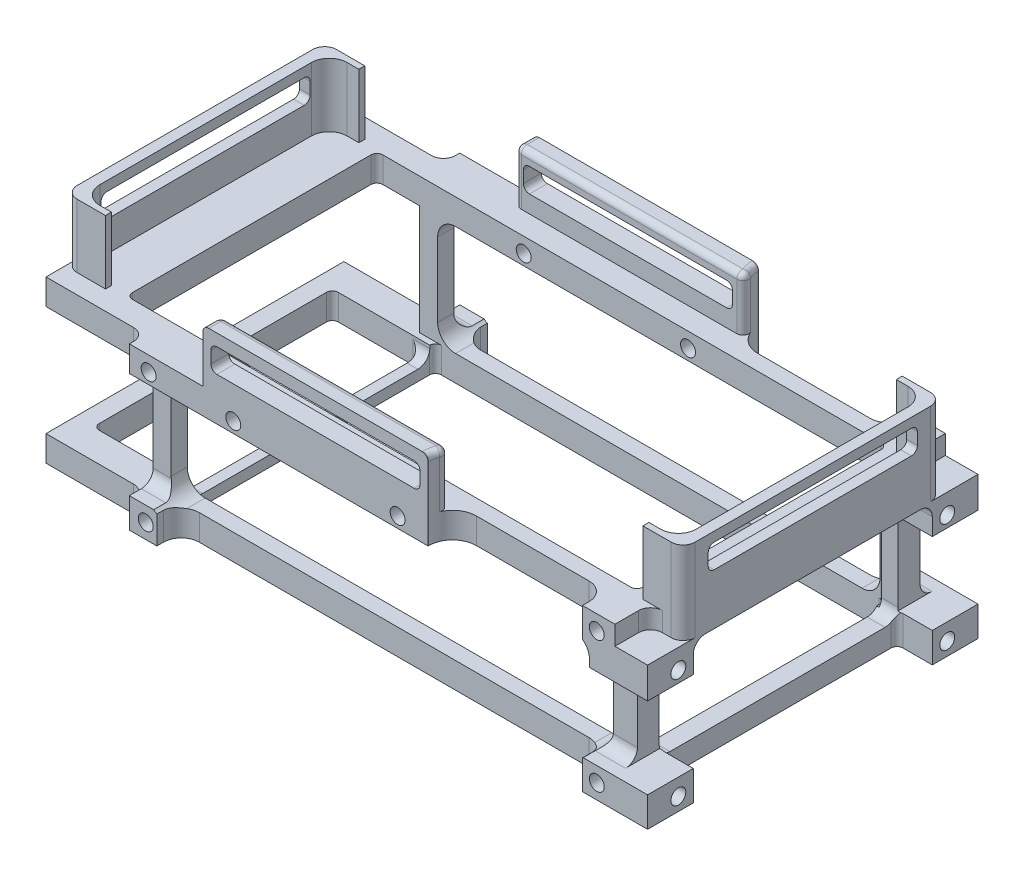
SolidWorks part; units mm, degrees
ref_plane "Front" through (0, 0, 0) normal (0, 0, 1) x (1, 0, 0)
ref_plane "Top" through (0, 0, 0) normal (0, 1, 0) x (1, 0, 0)
ref_plane "Right" through (0, 0, 0) normal (1, 0, 0) x (0, 0, -1)
sketch "草图1" plane through (0, 0, 0) normal (0, 1, 0) x (1, 0, 0)
  line L0 (-68.9333, 0) -> (79.9935, 0) construction
  line L1 (-51.7, 24.925) -> (-37.03, 24.925)
  line L2 (-35.03, 27.65) -> (-30.42, 27.65)
  line L3 (-51.7, 24.925) -> (-51.7, -24.925)
  line L4 (-35.03, -27.65) -> (-30.42, -27.65)
  line L5 (51.7, 27.65) -> (51.7, -27.65)
  line L8 (-35.03, 26.925) -> (-35.03, 27.65)
  line L9 (-30.42, 27.65) -> (-30.42, 26.55)
  line L10 (-27.42, 23.55) -> (37.8, 23.55)
  line L11 (40.8, 26.55) -> (40.8, 27.65)
  line L12 (40.8, 27.65) -> (51.7, 27.65)
  line L13 (-51.7, -24.925) -> (-37.03, -24.925)
  line L14 (-35.03, -26.925) -> (-35.03, -27.65)
  line L16 (-30.42, -27.65) -> (-30.42, -26.55)
  line L17 (-27.42, -23.55) -> (37.8, -23.55)
  line L18 (40.8, -26.55) -> (40.8, -27.65)
  line L19 (40.8, -27.65) -> (51.7, -27.65)
  arc A0 (37.8, -23.55) -> (40.8, -26.55) centre (37.8, -26.55) cw
  arc A1 (-30.42, -26.55) -> (-27.42, -23.55) centre (-27.42, -26.55) cw
  arc A2 (-30.42, 26.55) -> (-27.42, 23.55) centre (-27.42, 26.55) ccw
  arc A3 (37.8, 23.55) -> (40.8, 26.55) centre (37.8, 26.55) ccw
  arc A4 (-37.03, -24.925) -> (-35.03, -26.925) centre (-37.03, -26.925) cw
  arc A5 (-37.03, 24.925) -> (-35.03, 26.925) centre (-37.03, 26.925) ccw
  point P5 (0, 0)
  point P27 (-30.42, -23.55)
  point P30 (-30.42, 23.55)
  point P37 (-35.03, 24.925)
  dimension "D9" = 3
  dimension "D10" = 2
  dimension "D1" = 103.4
  dimension "D2" = 55.3
  dimension "D3" = 49.85
  dimension "D4" = 47.1
  dimension "D5" = 10.9
  dimension "D6" = 16.67
  dimension "D7" = 4.61
  dimension "D8" = 51.7
extrude "凸台-拉伸1" add sketch "草图1" along normal blind 27
sketch "草图2" plane through (0, 0, 0) normal (0, 0, 1) x (1, 0, 0)
  line L0 (-60.618, 13.5) -> (64.0258, 13.5) construction
  line L1 (-51.7, 22.7) -> (-35.03, 22.7)
  line L2 (-51.7, 27) -> (-51.7, 0) construction
  line L3 (-35.03, 27) -> (-35.03, 0) construction
  line L4 (-35.03, 22.7) -> (-35.03, 4.3)
  line L5 (-35.03, 4.3) -> (-51.7, 4.3)
  line L6 (-51.7, 4.3) -> (-58.4494, 4.3)
  line L7 (-58.4494, 4.3) -> (-58.4494, 22.7)
  line L8 (-58.4494, 22.7) -> (-51.7, 22.7)
  line L9 (-30.42, 27) -> (-30.42, 0) construction
  line L10 (-32.03, 19.7) -> (-32.03, 7.3)
  line L11 (-29.03, 4.3) -> (39, 4.3)
  line L12 (42, 7.3) -> (42, 19.7)
  line L13 (39, 22.7) -> (-29.03, 22.7)
  line L14 (51.7, 5) -> (46, 5)
  line L15 (51.7, 27) -> (51.7, 0) construction
  line L16 (46, 5) -> (46, 18.6)
  line L17 (46, 18.6) -> (55.971, 18.6)
  line L18 (55.971, 18.6) -> (51.7, 5)
  line L19 (40.8, 0) -> (51.7, 0) construction
  arc A0 (39, 4.3) -> (42, 7.3) centre (39, 7.3) ccw
  arc A1 (42, 19.7) -> (39, 22.7) centre (39, 19.7) ccw
  arc A2 (-29.03, 4.3) -> (-32.03, 7.3) centre (-29.03, 7.3) cw
  arc A3 (-32.03, 19.7) -> (-29.03, 22.7) centre (-29.03, 19.7) cw
  point P14 (-30.42, 13.5)
  dimension "D8" = 3
  dimension "D1" = 18.4
  dimension "D2" = 3
  dimension "D3" = 13.6
  dimension "D4" = 5
  dimension "D5" = 5.7
  dimension "D6" = 4
  dimension "D7" = 18.4
extrude "切除-拉伸1" cut sketch "草图2" against normal through all both and the other way through all
sketch "草图3" plane through (0, 27, 0) normal (0, 1, 0) x (1, 0, 0)
  line L0 (-59.4821, 0) -> (58.6559, 0) construction
  line L1 (-41.2022, 20.95) -> (42.2, 20.95)
  line L2 (-42.2022, 19.95) -> (-42.2022, -19.95)
  line L3 (-41.2022, -20.95) -> (42.2, -20.95)
  line L4 (43.2, 19.95) -> (43.2, -19.95)
  line L5 (51.7, -27.65) -> (51.7, 27.65) construction
  line L6 (37.8, 23.55) -> (-27.42, 23.55) construction
  arc A0 (-41.2022, 20.95) -> (-42.2022, 19.95) centre (-41.2022, 19.95) ccw
  arc A1 (-42.2022, -19.95) -> (-41.2022, -20.95) centre (-41.2022, -19.95) ccw
  arc A2 (42.2, -20.95) -> (43.2, -19.95) centre (42.2, -19.95) ccw
  arc A3 (42.2, 20.95) -> (43.2, 19.95) centre (42.2, 19.95) cw
  dimension "D4" = 1
  dimension "D1" = 8.5
  dimension "D2" = 85.4022
  dimension "D3" = 2.6
extrude "切除-拉伸2" cut sketch "草图3" against normal up to surface (22.7 mm away) up to face at (-41.1153, 4.3, 0)
sketch "草图4" plane through (0, 0, 0) normal (0, -1, 0) x (1, 0, 0)
  line L0 (-62.5801, 0) -> (74.4559, 0) construction
  line L1 (51.7, 27.65) -> (51.7, -27.65) construction
  line L2 (-47.7, 20) -> (-35.2, 20)
  line L3 (-48.7, 19) -> (-48.7, -19)
  line L4 (-47.7, -20) -> (-35.2, -20)
  line L5 (-34.2, 19) -> (-34.2, -19)
  line L6 (41.8, 20.95) -> (-31.4, 20.95)
  line L7 (42.8, 19.95) -> (42.8, -19.95)
  line L8 (41.8, -20.95) -> (-31.4, -20.95)
  line L9 (-32.4, 19.95) -> (-32.4, -19.95)
  line L10 (46.8, 20) -> (63.9751, 20)
  line L11 (45.8, 19) -> (45.8, -19)
  line L12 (46.8, -20) -> (63.9751, -20)
  line L13 (63.9751, 20) -> (63.9751, -20)
  line L15 (39, 20.95) -> (42.2, 20.95) construction
  line L16 (42.2, -20.95) -> (-41.2022, -20.95) construction
  line L17 (-51.7, -24.925) -> (-51.7, 24.925) construction
  arc A0 (45.8, -19) -> (46.8, -20) centre (46.8, -19) ccw
  arc A1 (46.8, 20) -> (45.8, 19) centre (46.8, 19) ccw
  arc A2 (42.8, -19.95) -> (41.8, -20.95) centre (41.8, -19.95) cw
  arc A3 (41.8, 20.95) -> (42.8, 19.95) centre (41.8, 19.95) cw
  arc A4 (-31.4, 20.95) -> (-32.4, 19.95) centre (-31.4, 19.95) ccw
  arc A5 (-31.4, -20.95) -> (-32.4, -19.95) centre (-31.4, -19.95) cw
  arc A6 (-35.2, -20) -> (-34.2, -19) centre (-35.2, -19) ccw
  arc A7 (-35.2, 20) -> (-34.2, 19) centre (-35.2, 19) cw
  arc A8 (-47.7, 20) -> (-48.7, 19) centre (-47.7, 19) ccw
  arc A9 (-48.7, -19) -> (-47.7, -20) centre (-47.7, -19) ccw
  dimension "D6" = 1
  dimension "D7" = 1
  dimension "D1" = 5.9
  dimension "D2" = 40
  dimension "D3" = 3
  dimension "D4" = 3
  dimension "D5" = 1.8
  dimension "D8" = 14.5
extrude "切除-拉伸3" cut sketch "草图4" against normal blind 5
sketch "草图5" plane through (0, 0, 0) normal (1, 0, 0) x (0, 0, -1)
  line L0 (0, 35.331) -> (0, -8.8082) construction
  line L1 (20, 0) -> (27.65, 0) construction
  line L2 (18, 23.5) -> (-18, 23.5)
  line L3 (20, 21.5) -> (20, 5.5)
  line L4 (18, 3.5) -> (-18, 3.5)
  line L5 (-20, 21.5) -> (-20, 5.5)
  line L6 (27.65, 18.6) -> (27.65, 5) construction
  line L7 (25.65, 18.6) -> (33.5193, 18.6)
  line L8 (23.65, 16.6) -> (23.65, 7)
  line L9 (25.65, 5) -> (33.5193, 5)
  line L10 (33.5193, 18.6) -> (33.5193, 5)
  line L11 (-38.9705, 13.5) -> (51.0717, 13.5) construction
  line L12 (-27.65, 27) -> (27.65, 27) construction
  line L13 (-27.65, 0) -> (-20, 0) construction
  line L14 (-33.5193, 18.6) -> (-33.5193, 5)
  line L15 (-25.65, 5) -> (-33.5193, 5)
  line L16 (-25.65, 18.6) -> (-33.5193, 18.6)
  line L17 (-23.65, 16.6) -> (-23.65, 7)
  arc A0 (18, 23.5) -> (20, 21.5) centre (18, 21.5) cw
  arc A1 (20, 5.5) -> (18, 3.5) centre (18, 5.5) cw
  arc A2 (-18, 3.5) -> (-20, 5.5) centre (-18, 5.5) cw
  arc A3 (-18, 23.5) -> (-20, 21.5) centre (-18, 21.5) ccw
  arc A4 (23.65, 7) -> (25.65, 5) centre (25.65, 7) ccw
  arc A5 (25.65, 18.6) -> (23.65, 16.6) centre (25.65, 16.6) ccw
  arc A6 (-23.65, 7) -> (-25.65, 5) centre (-25.65, 7) cw
  arc A7 (-25.65, 18.6) -> (-23.65, 16.6) centre (-25.65, 16.6) cw
  dimension "D4" = 2
  dimension "D1" = 2
  dimension "D2" = 20
  dimension "D3" = 40
  dimension "D5" = 4
  dimension "D6" = 13.6
  dimension "D7" = 5
extrude "切除-拉伸4" cut sketch "草图5" along normal through all contours L2 A3 L5 A2 L4 A1 L3 A0 region at (0, 13.5, 0)
extrude "切除-拉伸5" cut sketch "草图5<3>" against normal through all both and the other way through all contours A7 L16 L14 L15 A6 L17 | L7 A5 L8 A4 L9 L10 region at (0, 11.8, -28.6428) region at (0, 11.8, 28.6428)
sketch "草图5<3>" plane through (0, 0, 0) normal (1, 0, 0) x (0, 0, -1) same geometry as "草图5"
sketch "草图6" plane through (0, 0, 0) normal (1, 0, 0) x (0, 0, -1)
  line L0 (0, 30.8188) -> (0, -6.3575) construction
  line L1 (-20, 16.9293) -> (-20, 3.8)
  line L2 (-20, 18.6) -> (-20, 5.5) construction
  line L3 (-20, 0) -> (-20, 5) construction
  line L4 (-18, 1.8) -> (18, 1.8)
  line L5 (20, 5) -> (20, 0) construction
  line L6 (20, 3.8) -> (20, 15.6916)
  line L7 (20, 18.6) -> (20, 5.5) construction
  line L8 (20, 15.6916) -> (-20, 16.9293)
  line L9 (-19, 0) -> (19, 0) construction
  arc A0 (18, 1.8) -> (20, 3.8) centre (18, 3.8) ccw
  arc A1 (-20, 3.8) -> (-18, 1.8) centre (-18, 3.8) ccw
  point P19 (20, 1.8)
  point P22 (-20, 1.8)
  dimension "D2" = 2
  dimension "D1" = 1.8
extrude "切除-拉伸7" cut sketch "草图6" against normal blind 40
sketch "草图7" plane through (0, 27, 0) normal (0, 1, 0) x (1, 0, 0)
  line L0 (-69.6435, 0) -> (73.3117, 0) construction
  line L1 (-51.7, 24.925) -> (-51.7, -24.925) construction
  line L2 (-49.7, 21.7) -> (-44.97, 21.7)
  line L3 (-51.7, 19.7) -> (-51.7, -19.7)
  line L4 (-49.7, -21.7) -> (-44.97, -21.7)
  line L5 (-44.97, 21.7) -> (-44.97, 20.7)
  line L6 (-44.97, 20.7) -> (-46.92, 20.7)
  line L7 (-49.92, 17.7) -> (-49.92, -17.7)
  line L8 (-46.92, -20.7) -> (-44.97, -20.7)
  line L9 (-44.97, -20.7) -> (-44.97, -21.7)
  line L10 (0, 35.0593) -> (0, -43.9403) construction
  arc A0 (-51.7, -19.7) -> (-49.7, -21.7) centre (-49.7, -19.7) ccw
  arc A1 (-49.7, 21.7) -> (-51.7, 19.7) centre (-49.7, 19.7) ccw
  arc A2 (-49.92, -17.7) -> (-46.92, -20.7) centre (-46.92, -17.7) ccw
  arc A3 (-46.92, 20.7) -> (-49.92, 17.7) centre (-46.92, 17.7) ccw
  point P13 (-51.7, 21.7)
  dimension "D2" = 2
  dimension "D6" = 3
  dimension "D1" = 43.4
  dimension "D3" = 1.78
  dimension "D4" = 1
  dimension "D5" = 1
  dimension "D7" = 6.73
extrude "凸台-拉伸2" add sketch "草图7" along normal blind 10.65
sketch "草图9" plane through (0, 27, 0) normal (0, 1, 0) x (1, 0, 0)
  line L0 (-30.42, 27.65) -> (14.97, 27.65)
  line L1 (14.97, 27.65) -> (14.97, 23.55)
  line L2 (37.8, 23.55) -> (-27.42, 23.55) construction
  line L3 (14.97, 23.55) -> (-31.9047, 23.55)
  line L4 (-31.9047, 23.55) -> (-30.42, 27.65)
  line L5 (-61.7679, 0) -> (58.938, 0) construction
  line L6 (-31.9047, -23.55) -> (-30.42, -27.65)
  line L7 (14.97, -27.65) -> (14.97, -23.55)
  line L8 (14.97, -23.55) -> (-31.9047, -23.55)
  line L9 (-30.42, -27.65) -> (14.97, -27.65)
  dimension "D1" = 50
extrude "凸台-拉伸3" add sketch "草图9" against normal blind 10.65
extrude "切除-拉伸9" cut sketch "草图2<2>" against normal through all both and the other way through all contours L10 L0 L12 A1 L13 A3 | L0 L10 A2 L11 A0 L12 region at (4.985, 18.0776, 0) region at (4.985, 8.9224, 0)
sketch "草图2<2>" plane through (0, 0, 0) normal (0, 0, 1) x (1, 0, 0) same geometry as "草图2"
fillet "圆角1" radius 4 2 edges at (14.97, 24.85, -23.55) (14.97, 24.85, 23.55)
sketch "草图10" plane through (0, 27, 0) normal (0, 1, 0) x (1, 0, 0)
  line L0 (-22.73, 27.65) -> (-22.73, 24.65)
  line L1 (14.97, 27.65) -> (-35.03, 27.65) construction
  line L2 (-22.73, 24.65) -> (16.215, 24.65)
  line L3 (14.97, 27.65) -> (-22.73, 27.65)
  line L5 (-61.8704, 0) -> (68.9715, 0) construction
  line L6 (-22.73, -24.65) -> (16.215, -24.65)
  line L7 (-22.73, -27.65) -> (-22.73, -24.65)
  line L8 (14.97, -27.65) -> (-22.73, -27.65)
  arc A0 (14.97, 27.55) -> (18.97, 23.55) centre (18.97, 27.55) ccw construction
  arc A1 (14.97, 27.55) -> (18.97, 23.55) centre (18.97, 27.55) ccw
  arc A2 (14.97, -27.55) -> (18.97, -23.55) centre (18.97, -27.55) cw
  line M5 (-35.03, -27.65) -> (14.97, -27.65)
  line M6 (14.97, -27.65) -> (14.97, -27.55)
  arc M7 (14.97, -27.55) -> (18.97, -23.55) centre (18.97, -27.55) cw
  arc M17 (18.97, 23.55) -> (14.97, 27.55) centre (18.97, 27.55) cw
  line M18 (14.97, 27.55) -> (14.97, 27.65)
  line M19 (14.97, 27.65) -> (-35.03, 27.65)
  dimension "D1" = 3
extrude "凸台-拉伸4" add sketch "草图10" along normal blind 8.9 contours L7 L6 M5 M6 M7 | L0 L2 M17 M18 M19 region at (-3.6921, 27, -26.1422) region at (-3.6921, 27, 26.1422)
fillet "圆角2" radius 1 6 edges at (-22.73, 31.45, 24.65) (16.215, 31.45, 24.65) (-3.2575, 35.9, 24.65) (16.215, 31.45, -24.65) (-3.2575, 35.9, -24.65) (-22.73, 31.45, -24.65)
sketch "草图11" plane through (0, 0, 27.65) normal (0, 0, 1) x (1, 0, 0)
  line L0 (-3.88, 40.19) -> (-3.88, 18.3497) construction
  line L1 (-22.73, 35.9) -> (14.97, 35.9) construction
  line L2 (-20.38, 33.9) -> (12.62, 33.9)
  line L3 (-21.38, 32.9) -> (-21.38, 30.9)
  line L4 (-20.38, 29.9) -> (12.62, 29.9)
  line L5 (13.62, 32.9) -> (13.62, 30.9)
  arc A0 (12.62, 33.9) -> (13.62, 32.9) centre (12.62, 32.9) cw
  arc A1 (12.62, 29.9) -> (13.62, 30.9) centre (12.62, 30.9) ccw
  arc A2 (-21.38, 30.9) -> (-20.38, 29.9) centre (-20.38, 30.9) ccw
  arc A3 (-20.38, 33.9) -> (-21.38, 32.9) centre (-20.38, 32.9) ccw
  point P8 (-3.88, 35.9)
  dimension "D4" = 1
  dimension "D1" = 35
  dimension "D2" = 2
  dimension "D3" = 4
extrude "切除-拉伸10" cut sketch "草图11" against normal through all both and the other way through all
fillet "圆角3" radius 1 6 edges at (-22.4371, 35.6071, 24.9429) (-22.4371, 35.6071, -24.9429) (15.0457, 35.9, 26.7753) (-22.73, 35.9, 26.65) (15.0457, 35.9, -26.7753) (-22.73, 35.9, -26.65)
mirror "镜向1" about plane through (0, 0, 0) normal (1, 0, 0) of "凸台-拉伸2"
sketch "草图8" plane through (-51.7, 0, 0) normal (-1, 0, 0) x (0, 0, 1)
  line L0 (0, 41.7175) -> (0, 14.3238) construction
  line L1 (-16.5, 36.05) -> (16.5, 36.05)
  line L2 (-17.5, 35.05) -> (-17.5, 33.05)
  line L3 (-16.5, 32.05) -> (16.5, 32.05)
  line L4 (17.5, 35.05) -> (17.5, 33.05)
  line L5 (-19.7, 37.65) -> (19.7, 37.65) construction
  arc A0 (16.5, 32.05) -> (17.5, 33.05) centre (16.5, 33.05) ccw
  arc A1 (16.5, 36.05) -> (17.5, 35.05) centre (16.5, 35.05) cw
  arc A2 (-17.5, 33.05) -> (-16.5, 32.05) centre (-16.5, 33.05) ccw
  arc A3 (-16.5, 36.05) -> (-17.5, 35.05) centre (-16.5, 35.05) ccw
  dimension "D4" = 1
  dimension "D1" = 4
  dimension "D2" = 35
  dimension "D3" = 1.6
extrude "切除-拉伸8" cut sketch "草图8" against normal through all
sketch "草图12" plane through (0, 27, 0) normal (0, 1, 0) x (1, 0, 0)
  line L0 (46.24, 27.65) -> (46.24, 23.7)
  line L1 (51.7, 27.65) -> (40.8, 27.65) construction
  line L2 (44.97, 21.7) -> (49.7, 21.7) construction
  line L3 (48.24, 21.7) -> (49.7, 21.7)
  line L4 (46.24, 27.65) -> (47.6079, 31.5745)
  line L5 (47.6079, 31.5745) -> (57.0397, 29.6123)
  line L6 (57.0397, 29.6123) -> (51.7, 19.7)
  line L7 (51.7, 19.7) -> (51.7, 27.65) construction
  arc A0 (51.7, 19.7) -> (49.7, 21.7) centre (49.7, 19.7) ccw construction
  arc A1 (51.7, 19.7) -> (49.7, 21.7) centre (49.7, 19.7) ccw
  arc A2 (46.24, 23.7) -> (48.24, 21.7) centre (48.24, 23.7) ccw
  point P10 (46.24, 21.7)
  dimension "D1" = 2
  dimension "D2" = 5.46
extrude "切除-拉伸11" cut sketch "草图12" against normal blind 3.2
mirror "镜向2" about plane through (0, 0, 0) normal (0, 0, 1) of "切除-拉伸11"
sketch "草图13" plane through (-35.03, 0, 0) normal (-1, 0, 0) x (0, 0, 1)
  line L0 (-23.65, 15.1481) -> (-23.65, 20.7)
  line L1 (-23.65, 16.6) -> (-23.65, 7) construction
  line L2 (-24.925, 22.7) -> (24.925, 22.7) construction
  line L3 (-25.65, 22.7) -> (-29.4151, 22.7)
  line L4 (-29.4151, 22.7) -> (-31.0739, 15.1481)
  line L5 (-31.0739, 15.1481) -> (-23.65, 15.1481)
  arc A0 (-23.65, 20.7) -> (-25.65, 22.7) centre (-25.65, 20.7) ccw
  point P11 (-23.65, 22.7)
  dimension "D1" = 2
extrude "切除-拉伸12" cut sketch "草图13" against normal blind 10
mirror "镜向3" about plane through (0, 0, 0) normal (0, 0, 1) of "切除-拉伸12"
hole_wizard "M3 螺纹孔1" positions "草图15" profile "草图16" tap size "M3" standard "ISO" end condition through all
sketch "草图15" plane through (0, 0, 27.65) normal (0, 0, 1) x (1, 0, 0)
  line L0 (-43.006, 24.5) -> (23.4042, 24.5) construction
  line L2 (-27.42, 0) -> (37.8, 0) construction
  line L3 (-3.88, 35.9) -> (-3.88, 17.1352) construction
  line L4 (-21.73, 35.9) -> (13.97, 35.9) construction
  point P2 (-17.63, 24.5)
  point P4 (9.87, 24.5)
  point P31 (0, 0)
  dimension "D1" = 27.5
  dimension "D2" = 24.5
cosmetic thread "孔螺蚊线4" parameters "D2"=3
cosmetic thread "孔螺蚊线5" parameters "D2"=3
sketch "草图16" plane through (-17.63, 24.5, 27.65) normal (1, 0, 0) x (0, -1, 0)
  line L0 (0, 0) -> (0, 55.3)
  line L1 (0, 55.3) -> (1.25, 55.3)
  line L2 (1.25, 55.3) -> (1.25, 0)
  line L5 (1.25, 0) -> (0, 0)
  line L11 (0, -6.35) -> (0, 107.95) construction
  dimension "通孔螺纹孔钻头直径" = 2.5
  dimension "通孔螺纹孔钻头深度" = 55.3
hole_wizard "M3 螺纹孔2" positions "草图17" profile "草图18" tap size "M3" standard "ISO"
sketch "草图17" plane through (0, 0, 27.65) normal (0, 0, 1) x (1, 0, 0)
  line L0 (-35.4418, 24.5) -> (46.6109, 24.5) construction
  line L4 (51.7, 5) -> (51.7, 0) construction
  line L5 (-27.42, 0) -> (37.8, 0) construction
  point P0 (-31.8, 24.5)
  point P2 (-32.2806, 2.5)
  point P4 (43.2, 2.5)
  point P6 (43.2, 24.5)
  point P15 (0, 0)
  point P16 (0, 0)
  point P17 (0, 0)
  point P18 (47.0227, 24.1732)
  point P19 (43.6912, 2.5853)
  point P22 (0, 0)
  point P23 (0, 0)
  point P24 (43.6912, 24.55)
  point P25 (47.0227, 24.2772)
  point P26 (42.5435, 2.45)
  point P27 (0, 0)
  point P28 (42.6106, 2.45)
  dimension "D1" = 22
  dimension "D2" = 24.5
  dimension "D3" = 75
  dimension "D4" = 8.5
sketch "草图18" plane through (-31.8, 24.5, 27.65) normal (1, 0, 0) x (0, -1, 0)
  line L0 (0, 0) -> (0, 4.7217)
  line L1 (0, 4.7217) -> (1.25, 4)
  line L2 (1.25, 4) -> (1.25, 0)
  line L5 (1.25, 0) -> (0, 0)
  line L10 (0, 4.7217) -> (-1.25, 4) construction
  line L11 (0, -6.35) -> (0, 107.95) construction
  dimension "螺纹孔钻头直径" = 2.5
  dimension "螺纹孔钻头深度" = 4
  dimension "导头角度" = 120
cosmetic thread "孔螺蚊线7" parameters "D1"=4, "D2"=3
cosmetic thread "孔螺蚊线8" parameters "D1"=4, "D2"=3
cosmetic thread "孔螺蚊线9" parameters "D1"=4, "D2"=3
cosmetic thread "孔螺蚊线10" parameters "D1"=4, "D2"=3
hole_wizard "M3 螺纹孔3" positions "草图20" profile "草图21" tap size "M3" standard "ISO"
sketch "草图20" plane through (51.7, 0, 0) normal (1, 0, 0) x (0, 0, -1)
  line L0 (0, 38.7993) -> (0, -7.902) construction
  line L2 (20, 0) -> (27.65, 0) construction
  point P0 (-22.5, 20.5)
  point P2 (-22.5, 2.2)
  point P4 (22.5, 2.2)
  point P6 (22.5, 20.5)
  point P20 (0, 0)
  dimension "D1" = 45
  dimension "D2" = 18.3
  dimension "D3" = 2.2
sketch "草图21" plane through (51.7, 20.5, 22.5) normal (0, 1, 0) x (0, 0, -1)
  line L0 (0, 0) -> (0, 4.7217)
  line L1 (0, 4.7217) -> (1.25, 4)
  line L2 (1.25, 4) -> (1.25, 0)
  line L5 (1.25, 0) -> (0, 0)
  line L10 (0, 4.7217) -> (-1.25, 4) construction
  line L11 (0, -6.35) -> (0, 107.95) construction
  dimension "螺纹孔钻头直径" = 2.5
  dimension "螺纹孔钻头深度" = 4
  dimension "导头角度" = 120
cosmetic thread "孔螺蚊线11" parameters "D1"=4, "D2"=3
cosmetic thread "孔螺蚊线12" parameters "D1"=4, "D2"=3
cosmetic thread "孔螺蚊线13" parameters "D1"=4, "D2"=3
cosmetic thread "孔螺蚊线14" parameters "D1"=4, "D2"=3
mirror "镜向4" about plane through (0, 0, 0) normal (0, 0, 1) of "M3 螺纹孔2"
hole_wizard "M3 螺纹孔4" positions "草图22" profile "草图23" tap size "M3" standard "ISO"
sketch "草图22" plane through (-51.7, 0, 0) normal (-1, 0, 0) x (0, 0, 1)
  line L0 (0, 39.0231) -> (0, -9.3674) construction
  line L2 (-24.925, 0) -> (24.925, 0) construction
  point P0 (-22.5, 24.4)
  point P2 (-22.5, 2.4)
  point P4 (22.5, 2.4)
  point P6 (22.5, 24.4)
  point P15 (0, 0)
  point P16 (0, 0)
  point P17 (0, 0)
  point P18 (0, 0)
  point P19 (22.5, 2.3454)
  dimension "D1" = 22
  dimension "D2" = 45
  dimension "D3" = 2.4
sketch "草图23" plane through (-51.7, 24.4, -22.5) normal (0, 1, 0) x (0, 0, 1)
  line L0 (0, 0) -> (0, 4.7217)
  line L1 (0, 4.7217) -> (1.25, 4)
  line L2 (1.25, 4) -> (1.25, 0)
  line L5 (1.25, 0) -> (0, 0)
  line L10 (0, 4.7217) -> (-1.25, 4) construction
  line L11 (0, -6.35) -> (0, 107.95) construction
  dimension "螺纹孔钻头直径" = 2.5
  dimension "螺纹孔钻头深度" = 4
  dimension "导头角度" = 120
cosmetic thread "孔螺蚊线15" parameters "D1"=4, "D2"=3
cosmetic thread "孔螺蚊线16" parameters "D1"=4, "D2"=3
cosmetic thread "孔螺蚊线17" parameters "D1"=4, "D2"=3
cosmetic thread "孔螺蚊线18" parameters "D1"=4, "D2"=3
